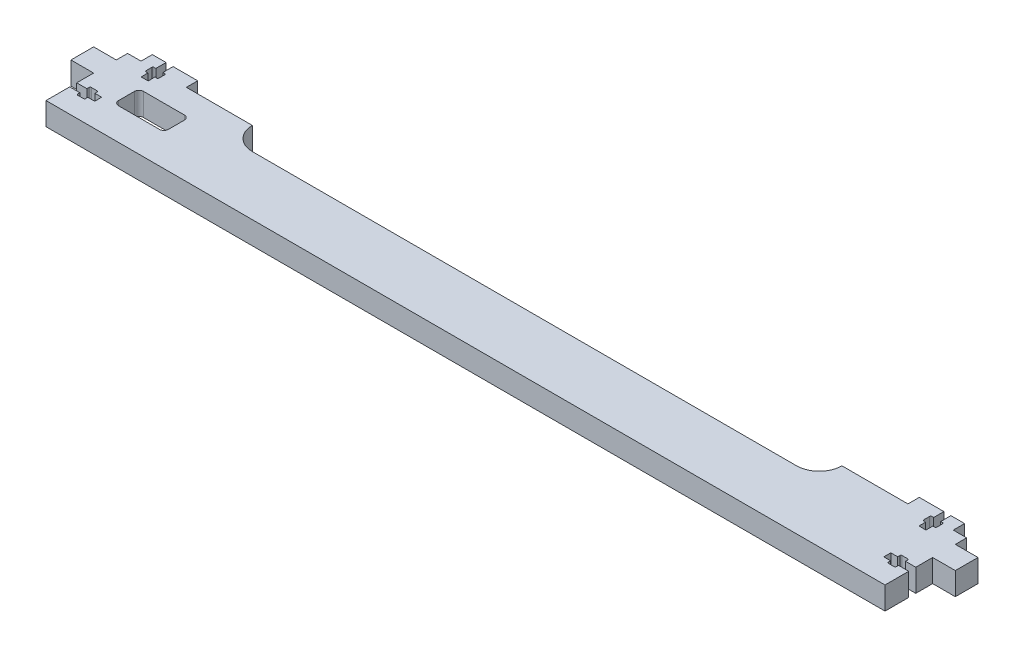
SolidWorks part; units mm, degrees
ref_plane "Front Plane" through (0, 0, 0) normal (0, 0, 1) x (1, 0, 0)
ref_plane "Top Plane" through (0, 0, 0) normal (0, 1, 0) x (1, 0, 0)
ref_plane "Right Plane" through (0, 0, 0) normal (1, 0, 0) x (0, 0, -1)
sketch "Sketch1" plane through (0, 0, 0) normal (0, 1, 0) x (1, 0, 0)
  line L0 (0, 18) -> (0, -18) construction
  line L1 (-185, 18) -> (0, 18)
  line L2 (-185, 18) -> (-185, 13)
  line L3 (-185, -18) -> (0, -18)
  line L4 (0, 18) -> (0, -18)
  line L5 (-185, 18) -> (0, 0) construction
  line L6 (-185, -18) -> (0, 0) construction
  line L7 (-185, 13) -> (-195, 13)
  line L8 (-195, 13) -> (-195, 3)
  line L9 (-195, 3) -> (-185, 3)
  line L10 (-185, 3) -> (-185, -18)
  point P0 (0, 0)
  dimension "D6" = 10
  dimension "D7" = 10
  dimension "D1" = 185
  dimension "D2" = 36
  dimension "D4" = 5
  dimension "D9" = 18
extrude "MainShape" add sketch "Sketch1" along normal blind 10 contours L2 L7 L8 L9 region at (-93.9423, 0, -0.1183)
sketch "Sketch15" plane through (0, 10, 0) normal (0, 1, 0) x (1, 0, 0)
  line L0 (-185, 18) -> (0, 18) construction
  line L1 (-159.1, 23) -> (-179.1, 23)
  line L2 (-159.1, 23) -> (-159.1, 13)
  line L3 (-159.1, 13) -> (-179.1, 13)
  line L4 (-179.1, 23) -> (-179.1, 13)
  line L5 (-159.1, 23) -> (-179.1, 13) construction
  line L6 (-159.1, 13) -> (-179.1, 23) construction
  line L7 (-185, 18) -> (-185, 13) construction
  point P0 (-169.1, 18)
  dimension "D1" = 20
  dimension "D2" = 5
  dimension "D3" = 15.9
extrude "Boss-Extrude4" add sketch "Sketch15" against normal through all
sketch "Sketch2" plane through (0, 10, 0) normal (0, 1, 0) x (1, 0, 0)
  line L0 (-171.5, 23) -> (-171.5, 12) construction
  line L2 (-173.05, 23) -> (-173.05, 18.5)
  line L3 (-173.05, 18.5) -> (-173.85, 18.5)
  line L4 (-174.35, 18) -> (-174.35, 15.5)
  line L5 (-173.85, 15) -> (-173.05, 15)
  line L6 (-173.05, 15) -> (-173.05, 12)
  line L7 (-173.05, 12) -> (-169.95, 12)
  line L8 (-185, 18) -> (-185, 13) construction
  line L9 (-173.05, 23) -> (-169.95, 23)
  line L10 (-169.95, 15) -> (-169.95, 12)
  line L11 (-169.15, 15) -> (-169.95, 15)
  line L12 (-168.65, 18) -> (-168.65, 15.5)
  line L13 (-169.95, 18.5) -> (-169.15, 18.5)
  line L14 (-169.95, 23) -> (-169.95, 18.5)
  line L16 (-185, -6) -> (-174, -6) construction
  line L17 (-159.1, 23) -> (-179.1, 23) construction
  line L50 (-185, 3) -> (-185, -18) construction
  line L51 (-174, -7.55) -> (-174, -4.45)
  line L52 (-174, -4.45) -> (-177, -4.45)
  line L53 (-177, -4.45) -> (-177, -3.5)
  line L54 (-177.5, -3) -> (-180, -3)
  line L55 (-180.5, -3.5) -> (-180.5, -4.45)
  line L56 (-180.5, -4.45) -> (-185, -4.45)
  line L57 (-185, -4.45) -> (-185, -7.55)
  line L58 (-195, 13) -> (-195, 3) construction
  line L59 (-180.5, -7.55) -> (-185, -7.55)
  line L60 (-180.5, -8.5) -> (-180.5, -7.55)
  line L61 (-177.5, -9) -> (-180, -9)
  line L62 (-177, -7.55) -> (-177, -8.5)
  line L63 (-174, -7.55) -> (-177, -7.55)
  arc A0 (-174.35, 15.5) -> (-173.85, 15) centre (-173.85, 15.5) ccw
  arc A1 (-173.85, 18.5) -> (-174.35, 18) centre (-173.85, 18) ccw
  arc A2 (-169.15, 18.5) -> (-168.65, 18) centre (-169.15, 18) cw
  arc A3 (-168.65, 15.5) -> (-169.15, 15) centre (-169.15, 15.5) cw
  arc A16 (-177, -3.5) -> (-177.5, -3) centre (-177.5, -3.5) ccw
  arc A17 (-180, -3) -> (-180.5, -3.5) centre (-180, -3.5) ccw
  arc A18 (-180, -9) -> (-180.5, -8.5) centre (-180, -8.5) cw
  arc A19 (-177, -8.5) -> (-177.5, -9) centre (-177.5, -8.5) cw
  point P14 (-174.35, 15)
  point P17 (-174.35, 18.5)
  point P28 (-168.65, 18.5)
  point P29 (-168.65, 15)
  point P34 (-195, 8)
  point P45 (-177, -3)
  point P48 (-180.5, -3)
  dimension "D8" = 0.5
  dimension "D16" = 0.5
  dimension "D1" = 11
  dimension "D2" = 1.55
  dimension "D3" = 1.55
  dimension "D5" = 2.85
  dimension "D6" = 3.5
  dimension "D7" = 13.5
  dimension "D9" = 11
  dimension "D10" = 8
  dimension "D11" = 3.5
  dimension "D12" = 3
  dimension "D13" = 1.55
  dimension "D14" = 1.55
  dimension "D15" = 14
  dimension "D4" = 8
extrude "ScrewSlots" cut sketch "Sketch2" against normal through all
mirror "Mirror1" about plane through (0, 0, 0) normal (1, 0, 0) of "Boss-Extrude4", "ScrewSlots", "MainShape"
sketch "Sketch6" plane through (0, 10, 0) normal (0, 1, 0) x (1, 0, 0)
  line L0 (0, -18) -> (0, -48) construction
  line L2 (-185, -18) -> (185, -18) construction
  line L3 (90, -48) -> (-90, -48)
  line L4 (-90, -48) -> (-120, -18)
  line L5 (90, -48) -> (120, -18)
  line L6 (-120, -18) -> (120, -18)
  dimension "D1" = 135
  dimension "D2" = 30
  dimension "D3" = 90
extrude "Boss-Extrude1" [suppressed] add sketch "Sketch6" against normal through all
sketch "Sketch8" plane through (0, 10, 0) normal (0, 1, 0) x (1, 0, 0)
  line L0 (-71.5, 4.8833) -> (-77.5, 4.8833) construction
  line L1 (-77, -1.6167) -> (-72, -1.6167)
  line L2 (-78, -0.6167) -> (-78, 4.3833)
  line L3 (-77, 5.3833) -> (-72, 5.3833)
  line L4 (-71, -0.6167) -> (-71, 4.3833)
  line L5 (-78, -1.6167) -> (-71, 5.3833) construction
  line L6 (-78, 5.3833) -> (-71, -1.6167) construction
  line L7 (-71.5, -1.1167) -> (-71.5, 4.8833) construction
  circle A0 centre (-74.5, -34.7667) radius 6.5
  circle A1 centre (-74.5, -15.8167) radius 5.5
  arc A2 (-77, -1.6167) -> (-78, -0.6167) centre (-77, -0.6167) cw
  circle A3 centre (-74.5, -34.7667) radius 6 construction
  circle A4 centre (-74.5, -15.8167) radius 3.5 construction
  arc A5 (-72, -1.6167) -> (-71, -0.6167) centre (-72, -0.6167) ccw
  arc A6 (-72, 5.3833) -> (-71, 4.3833) centre (-72, 4.3833) cw
  arc A7 (-78, 4.3833) -> (-77, 5.3833) centre (-77, 4.3833) cw
  point P6 (-74.5, 1.8833)
  dimension "D1" = 0.5
  dimension "D2" = 2
  dimension "D3" = 0.5
  dimension "D5" = 1
  dimension "D4" = 0.5
extrude "Cut-Extrude2" [suppressed] cut sketch "Sketch8" against normal through all
sketch "Sketch7" plane through (0, 10, 0) normal (0, 1, 0) x (1, 0, 0)
  circle A0 centre (60.5, -43.0167) radius 1.45
  circle A1 centre (-84.5, -43.0167) radius 1.45
  circle A2 centre (-84.5, 6.4833) radius 1.45
  circle A3 centre (60.5, 6.4833) radius 1.45
  dimension "D1" = 2.9
  dimension "D2" = 2.9
  dimension "D3" = 2.9
  dimension "D4" = 2.9
extrude "Cut-Extrude1" [suppressed] cut sketch "Sketch7" against normal through all
sketch "Sketch9" plane through (0, 10, 0) normal (0, 1, 0) x (1, 0, 0)
  line L0 (0, 7.2333) -> (0, -32.7667) construction
  line L1 (48.5, 7.2333) -> (-48.5, 7.2333) construction
  line L2 (-48.5, -32.7667) -> (48.5, -32.7667) construction
  line L3 (-48.5, -12.7667) -> (48.5, -12.7667) construction
  line L4 (-48.5, 7.2333) -> (-48.5, -32.7667) construction
  line L5 (48.5, -32.7667) -> (48.5, 7.2333) construction
  line L7 (-49, -33.2667) -> (49, -33.2667)
  line L8 (-49, -33.2667) -> (-49, 7.7333)
  line L9 (-49, 7.7333) -> (49, 7.7333)
  line L10 (49, -33.2667) -> (49, 7.7333)
  line L11 (-49, -33.2667) -> (49, 7.7333) construction
  line L12 (-49, 7.7333) -> (49, -33.2667) construction
  point P12 (0, -12.7667)
  dimension "D1" = 0.5
  dimension "D2" = 0.5
extrude "Cut-Extrude3" [suppressed] cut sketch "Sketch9" against normal through all and the other way through all
sketch "Sketch10" plane through (0, 10, 0) normal (0, 1, 0) x (1, 0, 0)
  line L0 (20, -39.2667) -> (20, -40.7667) construction
  line L1 (40, -39.2667) -> (0, -39.2667) construction
  line L2 (0, -40.7667) -> (40, -40.7667) construction
  line L3 (0, -40.0167) -> (40, -40.0167) construction
  line L4 (0, -39.2667) -> (0, -40.7667) construction
  line L5 (40, -40.7667) -> (40, -39.2667) construction
  line L7 (-0.2, -40.9667) -> (40.2, -40.9667)
  line L8 (-0.2, -40.9667) -> (-0.2, -39.0667)
  line L9 (-0.2, -39.0667) -> (40.2, -39.0667)
  line L10 (40.2, -40.9667) -> (40.2, -39.0667)
  line L11 (-0.2, -40.9667) -> (40.2, -39.0667) construction
  line L12 (-0.2, -39.0667) -> (40.2, -40.9667) construction
  point P12 (20, -40.0167)
  dimension "D1" = 0.2
  dimension "D2" = 0.2
extrude "Cut-Extrude4" [suppressed] cut sketch "Sketch10" against normal through all
sketch "Sketch12" [suppressed] plane through (0, 0, 0) normal (0, -1, 0) x (-1, 0, 0)
  line L1 (81.4, -9.8167) -> (67.6, -9.8167)
  line L2 (81.4, -9.8167) -> (81.4, -21.8167)
  line L3 (81.4, -21.8167) -> (67.6, -21.8167)
  line L4 (67.6, -9.8167) -> (67.6, -21.8167)
  line L5 (81.4, -9.8167) -> (67.6, -21.8167) construction
  line L6 (81.4, -21.8167) -> (67.6, -9.8167) construction
  point P0 (74.5, -15.8167)
  dimension "D1" = 13.8
  dimension "D2" = 12
extrude "PotentiometerAdjustment" [suppressed] cut sketch "Sketch12" against normal through all
sketch "Sketch11" plane through (0, 0, 0) normal (0, -1, 0) x (1, 0, 0)
  line L1 (-149, -7) -> (-167, -7)
  line L2 (-147, -5) -> (-147, 2)
  line L3 (-149, 4) -> (-167, 4)
  line L4 (-169, -5) -> (-169, 2)
  line L5 (-147, -7) -> (-169, 4) construction
  line L6 (-147, 4) -> (-169, -7) construction
  line L7 (173.05, -12) -> (169.95, -12) construction
  line L8 (-174, 7.55) -> (-174, 4.45) construction
  arc A0 (-147, 2) -> (-149, 4) centre (-149, 2) ccw
  arc A1 (-167, 4) -> (-169, 2) centre (-167, 2) ccw
  arc A2 (-167, -7) -> (-169, -5) centre (-167, -5) cw
  arc A3 (-149, -7) -> (-147, -5) centre (-149, -5) ccw
  point P0 (-158, -1.5)
  dimension "D3" = 2
  dimension "D1" = 22
  dimension "D2" = 11
  dimension "D4" = 5
  dimension "D5" = 5
extrude "LCDCableCutout" cut sketch "Sketch11" against normal through all
sketch "Sketch13" plane through (0, 10, 0) normal (0, 1, 0) x (1, 0, 0)
  line L0 (0, 18) -> (0, -18) construction
  line L1 (-169.95, 18) -> (169.95, 18) construction
  line L2 (-185, -18) -> (185, -18) construction
  line L3 (120, 18) -> (-120, 18) construction
  line L4 (120, 8) -> (-120, 8)
  line L5 (120, 28) -> (-120, 28)
  arc A0 (120, 8) -> (120, 28) centre (120, 18) ccw
  arc A1 (-120, 28) -> (-120, 8) centre (-120, 18) ccw
  point P8 (0, 18)
  dimension "D2" = 120
  dimension "D1" = 10
extrude "Cut-Extrude5" cut sketch "Sketch13" against normal through all
sketch "Sketch14" plane through (0, 10, 0) normal (0, 1, 0) x (1, 0, 0)
  line L1 (-169.95, 18) -> (169.95, 18) construction
  line L3 (-156.5, 18) -> (-156.5, 28) construction
  line L4 (-161.5, 18) -> (-151.5, 18)
  line L5 (-161.5, 18) -> (-161.5, 28)
  line L6 (-161.5, 28) -> (-151.5, 28)
  line L7 (-151.5, 18) -> (-151.5, 28)
  line L8 (-173.05, 12) -> (-169.95, 12) construction
  line L9 (154, 18) -> (154, 28) construction
  line L10 (149, 18) -> (149, 28)
  line L11 (159, 28) -> (149, 28)
  line L12 (159, 18) -> (159, 28)
  line L13 (159, 18) -> (149, 18)
  point P12 (-171.5, 12)
  dimension "D1" = 10
  dimension "D2" = 10
  dimension "D3" = 15
extrude "Boss-Extrude3" [suppressed] add sketch "Sketch14" against normal through all
equation "\"Y-ROD-SPACING\"=75"
equation "\"Y-BED-OFFSET\"=2"
equation "\"Y-BED-ROD-INSET\"=3.5"
equation "\"T-SLOT-NUT-FILLET-RADIUS\"=0.5"
equation "\"T-SLOT-SCREW-SHAFT-RADIUS\"=1.55"
equation "\"T-SLOT-SCREW-SHAFT-CUTOUT-LENGTH\"=11"
equation "\"T-SLOT-NUT-DEPTH\"=3.5"
equation "\"T-SLOT-NUT-WIDTH\"=2.85"
equation "\"T-SLOT-NUT-END-DISTANCE\"=8"
equation "\"ACRYLIC-TAB-CUTOUT-SIZE\"=\"ACRYLIC-THICKNESS\"+\"ACRYLIC-TAB-TOLERANCE\"*2"
equation "\"ACRYLIC-M3-HOLE\"=2.9"
equation "\"SMOOTHROD-CAP-SCREW-DISTANCE\"=20"
equation "\"D2@Sketch2\"=\"T-SLOT-SCREW-SHAFT-RADIUS\""
equation "\"D1@Sketch2\"=\"T-SLOT-SCREW-SHAFT-CUTOUT-LENGTH\""
equation "\"D6@Sketch2\"=\"T-SLOT-NUT-DEPTH\""
equation "\"D5@Sketch2\"=\"T-SLOT-NUT-WIDTH\""
equation "\"D3@Sketch2\"=\"T-SLOT-SCREW-SHAFT-RADIUS\""
equation "\"D8@Sketch2\"=\"T-SLOT-NUT-FILLET-RADIUS\""
equation "\"D4@Sketch2\"=\"T-SLOT-NUT-END-DISTANCE\""
equation "\"D11@Sketch2\"=\"T-SLOT-NUT-DEPTH\""
equation "\"D10@Sketch2\"=\"T-SLOT-NUT-END-DISTANCE\""
equation "\"D13@Sketch2\"=\"T-SLOT-SCREW-SHAFT-RADIUS\""
equation "\"D14@Sketch2\"=\"T-SLOT-SCREW-SHAFT-RADIUS\""
equation "\"D16@Sketch2\"=\"T-SLOT-NUT-FILLET-RADIUS\""
equation "\"D9@Sketch2\"=\"T-SLOT-SCREW-SHAFT-CUTOUT-LENGTH\""
equation "\"ACRYLIC-TAB-WIDTH\"=\"ACRYLIC-THICKNESS\""
equation "\"D6@Sketch1\"=\"ACRYLIC-TAB-WIDTH\""
equation "\"D7@Sketch1\"=\"ACRYLIC-TAB-WIDTH\""
equation "\"FRAME-WIDTH-INNER\"=370"
equation "\"D1@Sketch1\"=\"FRAME-WIDTH-INNER\"/2"
equation "\"X-ROD-SPACING\"=45"
equation "\"Z-ROD-SPACING\"=17.5"
equation "\"ACRYLIC-THICKNESS\"=10"
equation "\"ACRYLIC-THICKNESS2\"=4.5"
equation "\"NEMA17-HOLE-SPACING\"=31"
equation "\"NEMA17-CENTRAL-CUTOUT\"=22.5"
equation "\"Z-BRACKET-REACH\"=55"
equation "\"TOP-BRACKET-SPACING\"=40"
equation "\"SMOOTHROD-X-LENGTH\"=350"
equation "\"SMOOTHROD-Y-LENGTH\"=350"
equation "\"SMOOTHROD-Z-LENGTH\"=350"
equation "\"SMOOTHROD-TIGHTENING-HEADROOM\"=.25"
equation "\"LEADSCREW-Z-LENGTH\"=300"
equation "\"SCREW-LENGTH-FRAME\"=\"ACRYLIC-THICKNESS\" + 10"
equation "\"SCREW-HEAD-RADIUS\"=6"
equation "\"PRINTED-X-SMOOTHROD-DIAMETER\"=8.8"
equation "\"PRINTED-X-SMOOTHROD-CUTOUT\"=10"
equation "\"PRINTED-X-BASE-HEIGHT\"=10"
equation "\"PRINTED-LM8UU-CUTOUT-SIZE\"=15.5"
equation "\"PRINTED-LM8UU-CUTOUT-LENGTH\"=24.5"
equation "\"PRINTED-X-IDLER-HEIGHT\"=16"
equation "\"PSU-MOUNTING-WIDTH\"=95"
equation "\"PSU-MOUNTING-HEIGHT\"=177"
equation "\"D1@MainShape\"=\"ACRYLIC-THICKNESS\""
equation "\"Y-BELT-TO-ROD-DISTANCE\"=20"
equation "\"SPOOL-HOLDER-ROD-SPACING\"=150"
equation "\"Z-ROD-INSET\"=13.5"
equation "\"D7@Sketch2\"=\"Z-ROD-INSET\""
equation "\"D1@Sketch7\"=\"ACRYLIC-M3-HOLE\""
equation "\"D2@Sketch7\"=\"ACRYLIC-M3-HOLE\""
equation "\"D3@Sketch7\"=\"ACRYLIC-M3-HOLE\""
equation "\"D4@Sketch7\"=\"ACRYLIC-M3-HOLE\""
equation "\"Y-BED-SCREW-SPACING\"=209"
equation "\"Y-BED-SCREW-CUTOUT-SLOT-HEIGHT\"=2"
equation "\"ACRYLIC-TAB-TOLERANCE\"=-.05"
equation "\"SCREW-LENGTH-MOTOR\"=\"ACRYLIC-THICKNESS\" + 5"
equation "\"SCREW-LENGTH-EXTRUDER\"=28"
equation "\"PRINTED-M3-HOLE\"=3.5"
equation "\"PRINTED-M3-NUT-AF\"=6.25"
equation "\"ACRYLIC-X-CARRIAGE-WIDTH\"=55"
equation "\"ACRYLIC-X-CARRIAGE-HEIGHT\"=75"
equation "\"ACRYLIC-X-CARRIAGE-LM8UU-CUTOUT-WIDTH\"=24.25"
equation "\"ACRYLIC-X-CARRIAGE-LM8UU-CUTOUT-HEIGHT\"=11.0"
equation "\"ACRYLIC-X-CARRIAGE-SCREW-SPACING-X\"=15"
equation "\"ACRYLIC-X-CARRIAGE-SCREW-SPACING-Y\"=33"
equation "\"ACRYLIC-X-CARRIAGE-CENTER-TAB-SPACING\"=14"
equation "\"ACRYLIC-X-CARRIAGE-EXTRUDER-OFFSET\"=26"
equation "\"ACRYLIC-X-CARRIAGE-EXTRUDER-ANGLE\"=90"
equation "\"ACRYLIC-X-CARRIAGE-EXTRUDER-SHELF-DEPTH\"=\"ACRYLIC-X-CARRIAGE-EXTRUDER-OFFSET\" + 28"
equation "\"ACRYLIC-X-CARRIAGE-EXTRUDER-BRACE-SPACING\"=23"
equation "\"ACRYLIC-X-CARRIAGE-EXTRUDER-BRACE-TAB-OFFSET\"=20"
equation "\"ACRYLIC-X-CARRIAGE-EXTRUDER-BRACE-HEIGHT\"=35"
equation "\"ACRYLIC-X-CARRIAGE-EXTRUDER-BRACE-SCREW-SPACING\"=22"
equation "\"ACRYLIC-X-CARRIAGE-DUAL-WIDTH-MULTIPLIER\"=1.65"
equation "\"ACRYLIC-X-CARRIAGE-DUAL-HOTEND-SPACING\"=42"
equation "\"ACRYLIC-X-CARRIAGE-DUAL-WIDTH\"=75"
equation "\"ACRYLIC-X-CARRIAGE-DUAL-HOTEND-SEPARATION\"=36"
equation "\"ACRYLIC-X-CARRIAGE-DUAL-MOUNT-PLATE-DEPTH\"=75"
equation "\"ACRYLIC-X-CARRIAGE-DUAL-MOUNT-BRACE-WIDTH\"=33"
equation "\"ACRYLIC-X-CARRIAGE-DUAL-MOUNT-SCREW-WIDTH\"=40"
equation "\"BLOWER-FAN-WIDTH\"=15"
equation "\"D1@Sketch14\"=\"ACRYLIC-TAB-WIDTH\""
equation "\"D2@Sketch14\"=\"ACRYLIC-THICKNESS\""
equation "\"D3@Sketch15\"=\"Z-ROD-INSET\"+2.4"
